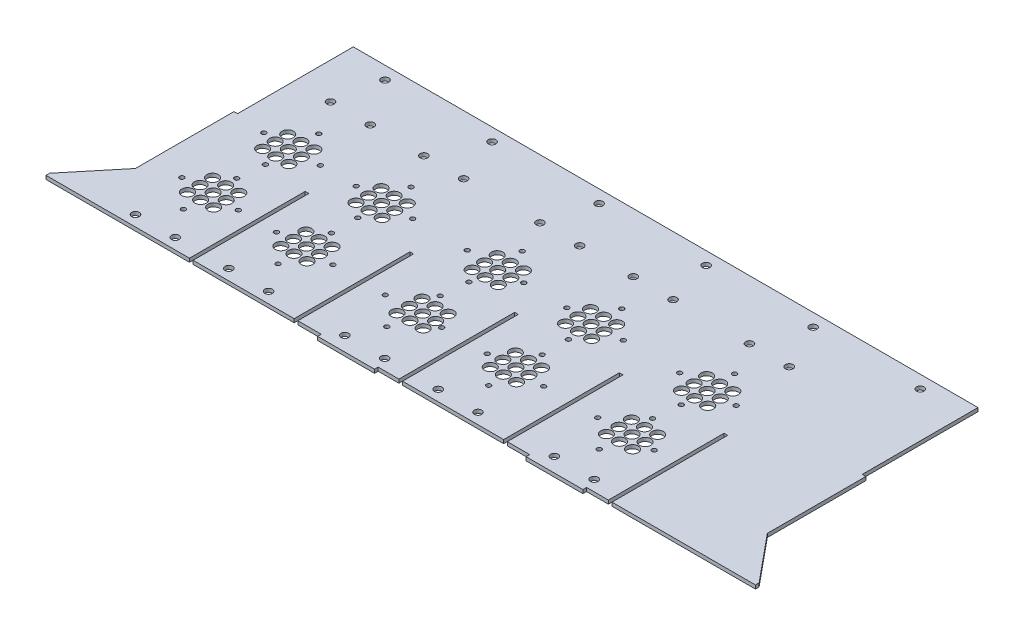
SolidWorks part; units mm, degrees
material "6061-T6 (SS)"
ref_plane "X-Y Datum" through (0, 0, 0) normal (0, 0, 1) x (1, 0, 0)
ref_plane "X-Z Datum" through (0, 0, 0) normal (0, 1, 0) x (1, 0, 0)
ref_plane "Y-Z Datum" through (0, 0, 0) normal (1, 0, 0) x (0, 0, -1)
sketch "Sketch1" plane through (0, 0, 0) normal (0, 0, 1) x (1, 0, 0)
  line L1 (-277.4525, -1.5875) -> (277.4525, -1.5875)
  line L2 (-277.4525, -1.5875) -> (-277.4525, 1.5875)
  line L3 (-277.4525, 1.5875) -> (277.4525, 1.5875)
  line L4 (277.4525, -1.5875) -> (277.4525, 1.5875)
  line L5 (-277.4525, -1.5875) -> (277.4525, 1.5875) construction
  line L6 (-277.4525, 1.5875) -> (277.4525, -1.5875) construction
  point P0 (0, 0)
  dimension "D1" = 554.9051
  dimension "D2" = 3.175
extrude "Boss-Extrude1" add sketch "Sketch1" along normal blind 232.6
sketch "Sketch2" plane through (0, 1.5875, 0) normal (0, 1, 0) x (1, 0, 0)
  line L0 (-176.5505, -181.8) -> (-277.4525, -181.8) construction
  line L1 (-277.4525, -232.6) -> (-277.4525, 0) construction
  line L3 (277.4525, -232.6) -> (-277.4525, -232.6) construction
  line L4 (-178.0615, -232.6) -> (-174.8865, -232.6)
  line L6 (-178.0615, -118.3) -> (-174.8865, -118.3)
  line L8 (-178.0615, -232.6) -> (-174.8865, -232.6)
  line L9 (-178.0615, -232.6) -> (-178.0615, -118.3)
  line L10 (-178.0615, -118.3) -> (-174.8865, -118.3)
  line L11 (-174.8865, -232.6) -> (-174.8865, -118.3)
  line L17 (-178.0615, -118.3) -> (-174.8865, -118.3)
  line L38 (-277.4525, 0) -> (-274.2775, 0)
  line L39 (-277.4525, 0) -> (-277.4525, -101.6)
  line L40 (-277.4525, -101.6) -> (-274.2775, -101.6)
  line L41 (-274.2775, 0) -> (-274.2775, -101.6)
  line L42 (277.4525, 0) -> (274.2775, 0)
  line L43 (277.4525, 0) -> (277.4525, -101.6)
  line L44 (277.4525, -101.6) -> (274.2775, -101.6)
  line L45 (274.2775, 0) -> (274.2775, -101.6)
  line M3 (277.4525, 0) -> (-277.4525, 0)
  line M4 (-277.4525, 0) -> (-277.4525, -232.6)
  line M6 (277.4525, -232.6) -> (277.4525, 0)
  dimension "D2" = 50.8
  dimension "D3" = 3.175
  dimension "D6" = 3.175
  dimension "D7" = 101.6
  dimension "D4" = 114.3
  dimension "D8" = 3.175
  dimension "D9" = 101.6
sketch "Sketch6" plane through (0, 0, 232.6) normal (0, 0, 1) x (1, 0, 0)
  line L0 (277.4525, 1.5875) -> (-277.4525, 1.5875) construction
  line L1 (-277.4525, 1.5875) -> (-277.4525, -1.5875) construction
  line L14 (163.1525, -1.5875) -> (163.1525, 1.5875)
  line L15 (113.1525, 1.5875) -> (163.1525, 1.5875)
  line L16 (113.1525, -1.5875) -> (163.1525, 1.5875) construction
  line L17 (113.1525, 1.5875) -> (163.1525, -1.5875) construction
  line L18 (113.1525, -1.5875) -> (163.1525, -1.5875)
  line L19 (113.1525, -1.5875) -> (113.1525, 1.5875)
  line L20 (-19.8055, -1.5875) -> (-19.8055, 1.5875)
  line L21 (-69.8055, 1.5875) -> (-19.8055, 1.5875)
  line L22 (-69.8055, -1.5875) -> (-19.8055, 1.5875) construction
  line L23 (-69.8055, 1.5875) -> (-19.8055, -1.5875) construction
  line L24 (-69.8055, -1.5875) -> (-19.8055, -1.5875)
  line L25 (-69.8055, -1.5875) -> (-69.8055, 1.5875)
  point P4 (-44.8055, 0)
  point P5 (138.1525, 0)
  dimension "D1" = 3.175
  dimension "D2" = 50
  dimension "D3" = 3.175
  dimension "D4" = 232.647
  dimension "D5" = 182.9581
sketch "Sketch7" plane through (0, -1.5875, 0) normal (0, -1, 0) x (-1, 0, 0)
  line L1 (-277.4525, -232.6) -> (-277.4525, 0) construction
  circle A2 centre (-234.7805, -11.2916) radius 3.302
  dimension "D1" = 42.672
  dimension "D2" = 6.604
extrude "Cut-Extrude4" cut sketch "Sketch7" against normal through all contours A2 region at (234.7805, -1.5875, 11.2916)
extrude "Boss-Extrude2" add sketch "Sketch6" along normal blind 3.175
pattern_linear "LPattern1" count 6 spacing 93.98 along (-1, 0, 0) of "Cut-Extrude4"
extrude "Cut-Extrude5" cut sketch "Sketch2" against normal through all contours L41 L40 M3 M4 | L45 L44 M3 M6 region at (275.865, 1.5875, 50.8) region at (-275.865, 1.5875, 50.8)
sketch "Sketch12" plane through (0, 1.5875, 0) normal (0, 1, 0) x (1, 0, 0)
  line L0 (-277.4525, -232.6) -> (-277.4525, -101.6) construction
  line L1 (-277.4525, -232.6) -> (-277.4525, -188.15)
  line L2 (277.4525, -232.6) -> (277.4525, -101.6) construction
  line L3 (277.4525, -232.6) -> (277.4525, -101.6)
  line L4 (-277.4525, -232.6) -> (-311.4885, -232.6)
  line L6 (-311.4885, -232.6) -> (-311.4885, -229.425)
  line L7 (-311.4885, -229.425) -> (-277.4525, -188.15)
  line M9 (-277.4525, -101.6) -> (-277.4525, -232.6)
  dimension "D1" = 34.036
  dimension "D2" = 44.45
  dimension "D3" = 3.175
extrude "Boss-Extrude3" add sketch "Sketch12" against normal blind 3.175 contours L4 M9 region at (-289.5542, 1.5875, 217.7128)
mirror "Mirror1" about plane through (0, 0, 0) normal (1, 0, 0) of "Boss-Extrude3"
sketch "Sketch13" plane through (0, -1.5875, 0) normal (0, -1, 0) x (1, 0, 0)
  line L0 (-185.4975, 232.6) -> (-185.4975, 131)
  line L1 (-311.4885, 232.6) -> (-69.8055, 232.6) construction
  line L2 (-274.2775, 0) -> (-274.2775, 101.6) construction
  line L3 (-185.4975, 232.6) -> (-182.3225, 232.6)
  line L5 (-185.4975, 232.6) -> (-185.4975, 131)
  line L6 (-185.4975, 131) -> (-182.3225, 131)
  line L7 (-182.3225, 232.6) -> (-182.3225, 131)
  line M23 (-69.8055, 232.6) -> (-311.4885, 232.6)
  dimension "D1" = 88.78
  dimension "D2" = 101.6
  dimension "D3" = 3.175
extrude "Cut-Extrude6" cut sketch "Sketch13" against normal through all contours L7 L0 L6 M23 region at (-183.91, -1.5875, 181.8)
pattern_linear "LPattern2" count 5 spacing 91.955 along (1, 0, 0) of "Cut-Extrude6"
sketch "Sketch14" plane through (0, 1.5875, 0) normal (0, 1, 0) x (1, 0, 0)
  circle A4 centre (-207.529, -51.825) radius 3 construction
  circle A5 centre (-242.454, -51.825) radius 3 construction
  circle A6 centre (-207.529, -223.075) radius 3 construction
  circle A7 centre (-242.454, -223.075) radius 3 construction
  circle A12 centre (-125.5715, -51.825) radius 3.3 construction
  circle A13 centre (-160.4965, -51.825) radius 3.3 construction
  circle A14 centre (-125.5715, -223.075) radius 3.3 construction
  circle A15 centre (-160.4965, -223.075) radius 3.3 construction
  point P24 (-207.529, -51.825)
  point P25 (-242.454, -51.825)
  point P26 (-207.529, -223.075)
  point P27 (-242.454, -223.075)
  point P28 (-125.5715, -51.825)
  point P29 (-160.4965, -51.825)
  point P30 (-125.5715, -223.075)
  point P31 (-160.4965, -223.075)
sketch "Sketch20" plane through (0, 7.935, 0) normal (0, 1, 0) x (1, 0, 0)
  circle A4 centre (-198.5909, -104.6371) radius 2
  circle A5 centre (-223.3764, -128.0582) radius 2
  circle A6 centre (-248.1619, -104.6371) radius 2
  circle A7 centre (-223.3764, -81.216) radius 2
  circle A16 centre (-167.1086, -174.6221) radius 2
  circle A17 centre (-142.323, -198.0432) radius 2
  circle A18 centre (-142.323, -151.201) radius 2
  circle A19 centre (-117.5375, -174.6221) radius 2
  circle A20 centre (-21.9991, -174.6221) radius 2
  circle A21 centre (-46.7846, -198.0432) radius 2
  circle A22 centre (-46.7846, -151.201) radius 2
  circle A23 centre (-71.5702, -174.6221) radius 2
  circle A32 centre (-117.5375, -104.6371) radius 2
  circle A33 centre (-142.323, -128.0582) radius 2
  circle A34 centre (-167.1086, -104.6371) radius 2
  circle A35 centre (-142.323, -81.216) radius 2
  circle A36 centre (-200.6251, -174.6221) radius 2
  circle A37 centre (-225.4106, -198.0432) radius 2
  circle A38 centre (-250.1962, -174.6221) radius 2
  circle A39 centre (-225.4106, -151.201) radius 2
  circle A44 centre (-44.7504, -128.0582) radius 2
  circle A45 centre (-19.9649, -104.6371) radius 2
  circle A46 centre (-44.7504, -81.216) radius 2
  circle A47 centre (-69.5359, -104.6371) radius 2
  circle A56 centre (42.677, -198.0432) radius 2
  circle A57 centre (67.4625, -174.6221) radius 2
  circle A58 centre (42.677, -151.201) radius 2
  circle A59 centre (17.8914, -174.6221) radius 2
  circle A60 centre (42.677, -128.0582) radius 2
  circle A61 centre (17.8914, -104.6371) radius 2
  circle A62 centre (67.4625, -104.6371) radius 2
  circle A63 centre (42.677, -81.216) radius 2
  circle A72 centre (139.7154, -198.0432) radius 2
  circle A73 centre (114.9298, -174.6221) radius 2
  circle A74 centre (164.5009, -174.6221) radius 2
  circle A75 centre (139.7154, -151.201) radius 2
  circle A76 centre (166.5351, -104.6371) radius 2
  circle A77 centre (141.7496, -128.0582) radius 2
  circle A78 centre (116.9641, -104.6371) radius 2
  circle A79 centre (141.7496, -81.216) radius 2
extrude "Cut-Extrude8" cut sketch "Sketch20" against normal through all
sketch "Sketch21" plane through (0, 1.5875, 0) normal (0, 1, 0) x (1, 0, 0)
  circle A5 centre (-224.9915, -95.3433) radius 5
  circle A6 centre (-236.4915, -95.3433) radius 5
  circle A7 centre (-236.4915, -106.3433) radius 5
  circle A8 centre (-236.4915, -117.3433) radius 5
  circle A11 centre (-213.4915, -106.3433) radius 5
  circle A12 centre (-224.9915, -106.3433) radius 5
  circle A16 centre (-224.9915, -117.3433) radius 5
  circle A17 centre (-213.4915, -117.3433) radius 5
  circle A18 centre (-213.4915, -95.3433) radius 5
  circle A46 centre (-236.4915, -183.3433) radius 5
  circle A47 centre (-224.9915, -183.3433) radius 5
  circle A48 centre (-213.4915, -183.3433) radius 5
  circle A49 centre (-213.4915, -172.3433) radius 5
  circle A50 centre (-213.4915, -161.3433) radius 5
  circle A51 centre (-224.9915, -161.3433) radius 5
  circle A52 centre (-224.9915, -172.3433) radius 5
  circle A53 centre (-236.4915, -172.3433) radius 5
  circle A54 centre (-236.4915, -161.3433) radius 5
extrude "Cut-Extrude9" cut sketch "Sketch21" against normal through all
pattern_linear "LPattern5" count 3 spacing 183.896 along (1, 0, 0) of "Cut-Extrude9"
sketch "Sketch22" plane through (0, 1.5875, 0) normal (0, 1, 0) x (1, 0, 0)
  circle A9 centre (-131.534, -117.3433) radius 5
  circle A10 centre (-143.034, -117.3433) radius 5
  circle A11 centre (-154.534, -117.3433) radius 5
  circle A12 centre (-154.534, -106.3433) radius 5
  circle A13 centre (-143.034, -106.3433) radius 5
  circle A14 centre (-131.534, -106.3433) radius 5
  circle A15 centre (-131.534, -95.3433) radius 5
  circle A16 centre (-143.034, -95.3433) radius 5
  circle A17 centre (-154.534, -95.3433) radius 5
  circle A27 centre (-131.534, -183.3433) radius 5
  circle A28 centre (-131.534, -172.3433) radius 5
  circle A29 centre (-131.534, -161.3433) radius 5
  circle A30 centre (-143.034, -161.3433) radius 5
  circle A31 centre (-143.034, -172.3433) radius 5
  circle A32 centre (-143.034, -183.3433) radius 5
  circle A33 centre (-154.534, -183.3433) radius 5
  circle A34 centre (-154.534, -172.3433) radius 5
  circle A35 centre (-154.534, -161.3433) radius 5
extrude "Cut-Extrude10" cut sketch "Sketch22" against normal through all
pattern_linear "LPattern6" count 2 spacing 183.896 along (1, 0, 0) of "Cut-Extrude10"
hole_wizard "M6 Clearance Hole2" positions "Sketch14" profile "Sketch24" hole size "M6" standard "ANSI Metric" end condition through all
sketch "Sketch24" plane through (-160.4965, 1.5875, 223.075) normal (1, 0, 0) x (0, 0, 1)
  line L0 (0, 0) -> (0, 3.175)
  line L1 (0, 3.175) -> (3.3, 3.175)
  line L2 (3.3, 3.175) -> (3.3, 0)
  line L5 (3.3, 0) -> (0, 0)
  line L11 (0, -6.35) -> (0, 107.95) construction
  dimension "Thru Hole Dia." = 6.6
  dimension "Thru Hole Depth" = 3.175
pattern_linear "LPattern7" count 2 spacing 183.896 along (1, 0, 0) of "M6 Clearance Hole2"
sketch "Sketch25" plane through (0, 1.5875, 0) normal (0, 1, 0) x (1, 0, 0)
  circle A0 centre (125.423, -51.825) radius 3
  circle A1 centre (160.348, -51.825) radius 3
  circle A2 centre (125.423, -223.075) radius 3
  circle A3 centre (160.348, -223.075) radius 3
  point P1 (125.423, -51.825)
  point P4 (160.348, -51.825)
  point P9 (125.423, -223.075)
  point P11 (160.348, -223.075)
  dimension "D1" = 34.925
  dimension "D2" = 34.925
hole_wizard "M6 Clearance Hole3" positions "Sketch25" profile "Sketch26" hole size "M6" standard "ANSI Metric" end condition through all
sketch "Sketch26" plane through (125.423, 1.5875, 51.825) normal (1, 0, 0) x (0, 0, 1)
  line L0 (0, 0) -> (0, 3.175)
  line L1 (0, 3.175) -> (3.3, 3.175)
  line L2 (3.3, 3.175) -> (3.3, 0)
  line L5 (3.3, 0) -> (0, 0)
  line L11 (0, -6.35) -> (0, 107.95) construction
  dimension "Thru Hole Dia." = 6.6
  dimension "Thru Hole Depth" = 3.175
